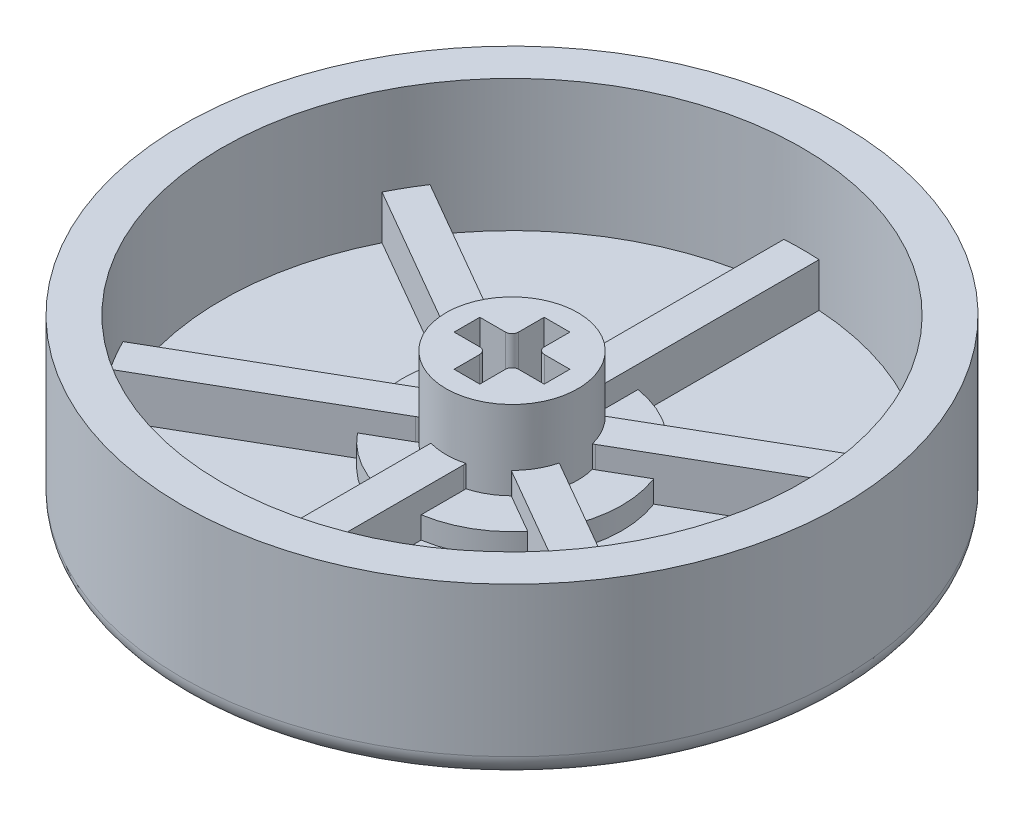
SolidWorks part; units mm, degrees
ref_plane "Front Plane" through (0, 0, 0) normal (0, 0, 1) x (1, 0, 0)
ref_plane "Top Plane" through (0, 0, 0) normal (0, 1, 0) x (1, 0, 0)
ref_plane "Right Plane" through (0, 0, 0) normal (1, 0, 0) x (0, 0, -1)
sketch "Sketch1" plane through (0, 0, 0) normal (0, 1, 0) x (1, 0, 0)
  circle A0 centre (0, 0) radius 15
  dimension "D1" = 30
extrude "button top" add sketch "Sketch1" along normal blind 1.8
sketch "Sketch2" plane through (0, 1.8, 0) normal (0, 1, 0) x (1, 0, 0)
  circle A3 centre (0, 0) radius 15
  circle A4 centre (0, 0) radius 15 construction
  circle A5 centre (0, 0) radius 13.2
  dimension "D1" = 1.8
extrude "button walls" add sketch "Sketch2" along normal blind 6
sketch "Sketch5" plane through (0, 1.8, 0) normal (0, 1, 0) x (1, 0, 0)
  circle A0 centre (0, 0) radius 5
  dimension "D1" = 10
extrude "offset" add sketch "Sketch5" along normal blind 1
sketch "Sketch3" plane through (0, 1.8, 0) normal (0, 1, 0) x (1, 0, 0)
  line L0 (0, -2.05) -> (0, 2.05) construction
  line L1 (-2.05, 0) -> (2.05, 0) construction
  line L2 (-0.585, 0.885) -> (-0.585, 2.05)
  line L3 (-0.585, -2.05) -> (0.585, -2.05)
  line L4 (-0.585, -2.05) -> (-0.585, -0.885)
  line L5 (-0.585, 2.05) -> (0.585, 2.05)
  line L6 (0.585, -2.05) -> (0.585, -0.885)
  line L7 (-0.585, -2.05) -> (0.585, 2.05) construction
  line L8 (-0.585, 2.05) -> (0.585, -2.05) construction
  line L9 (-2.05, -0.585) -> (-0.885, -0.585)
  line L10 (-2.05, -0.585) -> (-2.05, 0.585)
  line L11 (-2.05, 0.585) -> (-0.885, 0.585)
  line L12 (2.05, -0.585) -> (2.05, 0.585)
  line L13 (-2.05, -0.585) -> (2.05, 0.585) construction
  line L14 (-2.05, 0.585) -> (2.05, -0.585) construction
  line L15 (0.885, 0.585) -> (2.05, 0.585)
  line L16 (0.585, 0.885) -> (0.585, 2.05)
  line L17 (0.885, -0.585) -> (2.05, -0.585)
  circle A0 centre (0, 0) radius 3
  arc A1 (-0.585, -0.885) -> (-0.885, -0.585) centre (-0.885, -0.885) ccw
  arc A2 (0.585, -0.885) -> (0.885, -0.585) centre (0.885, -0.885) cw
  arc A3 (0.885, 0.585) -> (0.585, 0.885) centre (0.885, 0.885) cw
  arc A4 (-0.585, 0.885) -> (-0.885, 0.585) centre (-0.885, 0.885) cw
  point P6 (0, 0)
  point P9 (0, 0)
  point P22 (2.05, 0)
  point P24 (0, 2.05)
  point P29 (0.585, -0.585)
  point P32 (0.585, 0.585)
  dimension "D1" = 6
  dimension "D4" = 0.3
  dimension "D2" = 4.1
  dimension "D3" = 1.17
extrude "stem housing" add sketch "Sketch3" along normal blind 3.6 from surface starting at face at (0, 2.8, 5)
sketch "Sketch4" plane through (0, 1.8, 0) normal (0, 1, 0) x (1, 0, 0)
  line L0 (0, 3) -> (0, 13.2) construction
  line L1 (-0.8, 3) -> (-0.8, 13.2)
  line L2 (0.8, 3) -> (0.8, 13.2)
  line L3 (2.5981, 1.5) -> (11.4315, 6.6) construction
  line L4 (2.1981, 2.1928) -> (11.0315, 7.2928)
  line L5 (2.9981, 0.8072) -> (11.8315, 5.9072)
  line L6 (2.5981, -1.5) -> (11.4315, -6.6) construction
  line L7 (2.9981, -0.8072) -> (11.8315, -5.9072)
  line L8 (2.1981, -2.1928) -> (11.0315, -7.2928)
  line L9 (0, -3) -> (0, -13.2) construction
  line L10 (0.8, -3) -> (0.8, -13.2)
  line L11 (-0.8, -3) -> (-0.8, -13.2)
  line L12 (-2.5981, -1.5) -> (-11.4315, -6.6) construction
  line L13 (-2.1981, -2.1928) -> (-11.0315, -7.2928)
  line L14 (-2.9981, -0.8072) -> (-11.8315, -5.9072)
  line L15 (-2.5981, 1.5) -> (-11.4315, 6.6) construction
  line L16 (-2.9981, 0.8072) -> (-11.8315, 5.9072)
  line L17 (-2.1981, 2.1928) -> (-11.0315, 7.2928)
  circle A0 centre (0, 0) radius 3 construction
  circle A1 centre (0, 0) radius 3 construction
  circle A2 centre (0, 0) radius 13.2 construction
  arc A3 (-0.8, 3) -> (0.8, 3) centre (0, 3) ccw
  arc A4 (0.8, 13.2) -> (-0.8, 13.2) centre (0, 13.2) ccw
  arc A5 (2.1981, 2.1928) -> (2.9981, 0.8072) centre (2.5981, 1.5) ccw
  arc A6 (11.8315, 5.9072) -> (11.0315, 7.2928) centre (11.4315, 6.6) ccw
  arc A7 (2.9981, -0.8072) -> (2.1981, -2.1928) centre (2.5981, -1.5) ccw
  arc A8 (11.0315, -7.2928) -> (11.8315, -5.9072) centre (11.4315, -6.6) ccw
  arc A9 (0.8, -3) -> (-0.8, -3) centre (0, -3) ccw
  arc A10 (-0.8, -13.2) -> (0.8, -13.2) centre (0, -13.2) ccw
  arc A11 (-2.1981, -2.1928) -> (-2.9981, -0.8072) centre (-2.5981, -1.5) ccw
  arc A12 (-11.8315, -5.9072) -> (-11.0315, -7.2928) centre (-11.4315, -6.6) ccw
  arc A13 (-2.9981, 0.8072) -> (-2.1981, 2.1928) centre (-2.5981, 1.5) ccw
  arc A14 (-11.0315, 7.2928) -> (-11.8315, 5.9072) centre (-11.4315, 6.6) ccw
  point P9 (0, 8.1)
  point P18 (7.0148, 4.05)
  point P25 (7.0148, -4.05)
  point P32 (0, -8.1)
  point P39 (-7.0148, -4.05)
  point P46 (-7.0148, 4.05)
  point P51 (0, 0)
  dimension "D1" = 1.6
  dimension "D2" = 6
extrude "Boss-Extrude4" add sketch "Sketch4" along normal blind 2
fillet "Fillet1" radius 1 1 edges at (0, 0, 15)
